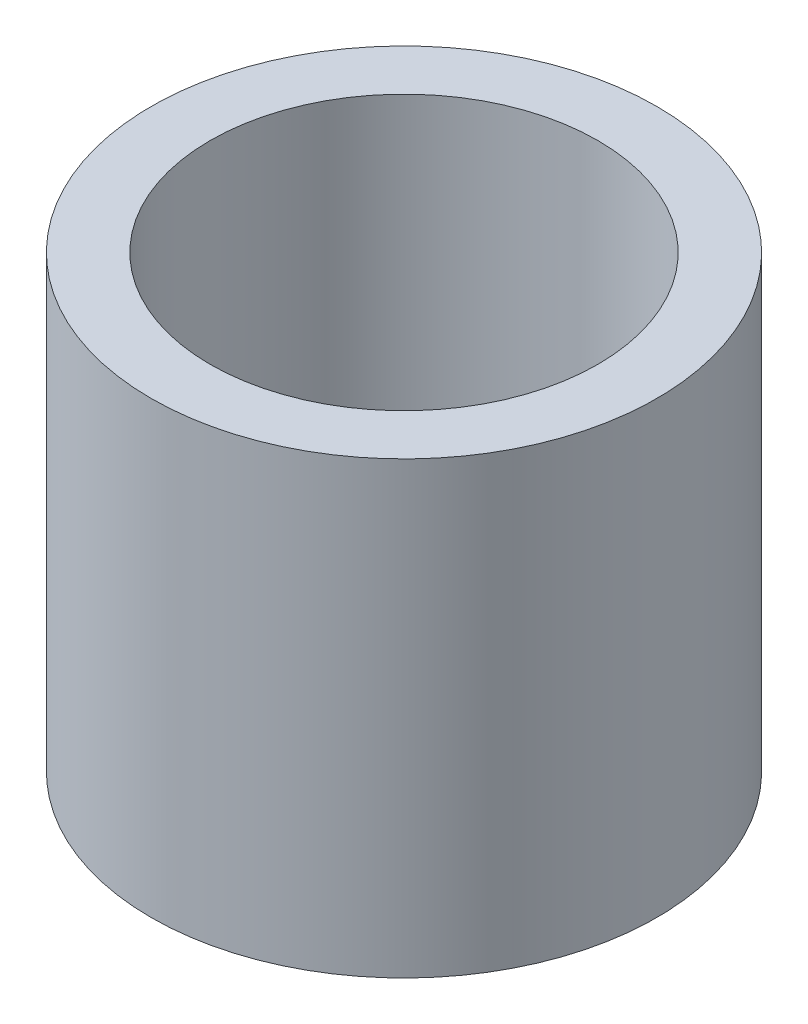
SolidWorks part; units mm, degrees
material "OMD-98"
ref_plane "Front Plane" through (0, 0, 0) normal (0, 0, 1) x (1, 0, 0)
ref_plane "Top Plane" through (0, 0, 0) normal (0, 1, 0) x (1, 0, 0)
ref_plane "Right Plane" through (0, 0, 0) normal (1, 0, 0) x (0, 0, -1)
sketch "Sketch1" plane through (0, 0, 0) normal (0, 1, 0) x (1, 0, 0)
  circle A0 centre (0, 0) radius 6.9
  circle A1 centre (0, 0) radius 9
  dimension "D1" = 18
  dimension "D2" = 13.8
extrude "Boss-Extrude1" add sketch "Sketch1" along normal blind 16
